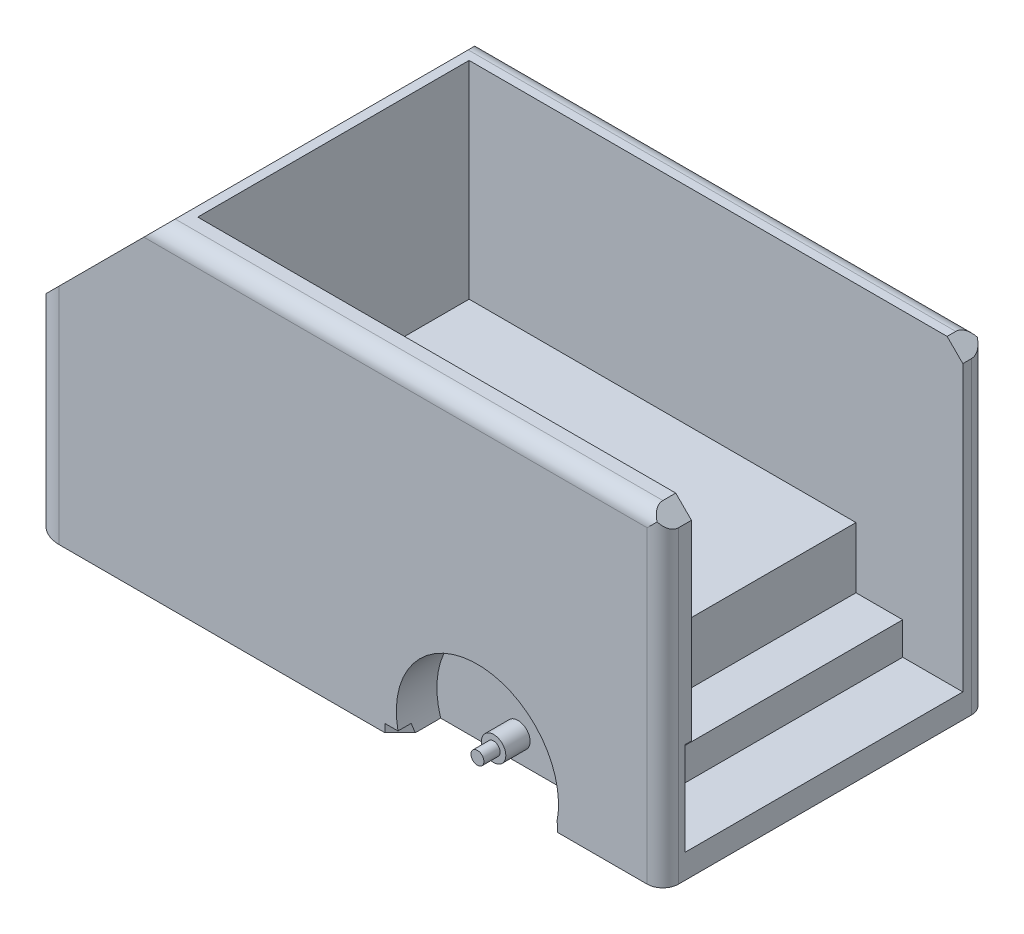
SolidWorks part; units mm, degrees
ref_plane "Front Plane" through (0, 0, 0) normal (0, 0, 1) x (1, 0, 0)
ref_plane "Top Plane" through (0, 0, 0) normal (0, 1, 0) x (1, 0, 0)
ref_plane "Right Plane" through (0, 0, 0) normal (1, 0, 0) x (0, 0, -1)
sketch "Sketch1" plane through (0, 0, 0) normal (0, 1, 0) x (1, 0, 0)
  line L0 (14.509, 50.8) -> (22.488, 42.821)
  line L1 (-101.6, 50.8) -> (14.509, 50.8)
  line L2 (-101.6, 50.8) -> (-101.6, -50.8)
  line L3 (-101.6, -50.8) -> (14.509, -50.8)
  line L4 (101.6, 50.8) -> (101.6, -50.8)
  line L5 (-101.6, 50.8) -> (101.6, -50.8) construction
  line L6 (-101.6, -50.8) -> (101.6, 50.8) construction
  line L7 (22.488, 42.821) -> (37.3964, 42.821)
  line L8 (37.3964, 42.821) -> (37.3964, 38.7247)
  line L9 (37.3964, 38.7247) -> (49.6575, 38.7247)
  line L10 (49.6575, 38.7247) -> (49.6575, 42.821)
  line L11 (49.6575, 42.821) -> (57.4229, 42.821)
  line L13 (-112.3935, 0) -> (135.4852, 0) construction
  line L15 (49.6575, -42.821) -> (57.4229, -42.821)
  line L16 (49.6575, -38.7247) -> (49.6575, -42.821)
  line L17 (37.3964, -38.7247) -> (49.6575, -38.7247)
  line L18 (37.3964, -42.821) -> (37.3964, -38.7247)
  line L19 (22.488, -42.821) -> (37.3964, -42.821)
  line L20 (14.509, -50.8) -> (22.488, -42.821)
  line L21 (68.6622, 50.8) -> (101.6, 50.8)
  line L22 (68.6622, -50.8) -> (101.6, -50.8)
  spline S0 degree 2 poles (57.4229, 42.821) (65.476, 42.6296) (68.6622, 50.8) knots 0 0 0 1 1 1
  spline S1 degree 2 poles (57.4229, -42.821) (65.476, -42.6296) (68.6622, -50.8) knots 0 0 0 1 1 1
  point P0 (0, 0)
  dimension "D1" = 101.6
  dimension "D2" = 203.2
extrude "Boss-Extrude1" add sketch "Sketch1" along normal blind 2.54
sketch "Sketch2" plane through (0, 2.54, 0) normal (0, 1, 0) x (1, 0, 0)
  line L1 (-101.6, 50.8) -> (101.6, 50.8)
  line L2 (-101.6, 50.8) -> (-101.6, -50.8)
  line L3 (-101.6, -50.8) -> (101.6, -50.8)
  line L4 (101.6, 50.8) -> (101.6, -50.8)
extrude "Boss-Extrude2" add sketch "Sketch2" along normal blind 99.06
chamfer "Chamfer2" distance 45.56 angle 45 1 edges at (-101.6, 101.6, 0)
chamfer "Chamfer3" distance 4.92 angle 45 1 edges at (101.6, 101.6, 0)
chamfer "Chamfer4" distance 4.92 angle 45 1 edges at (-101.6, 0, 0)
fillet "Fillet1" radius 4.92 2 edges at (20.32, 101.6, -50.8) (20.32, 101.6, 50.8)
fillet "Fillet3" radius 4.92 2 edges at (101.6, 48.34, 50.8) (101.6, 48.34, -50.8)
chamfer "Chamfer5" distance 10 angle 45 2 edges at (-101.6, 30.48, -50.8) (-101.6, 30.48, 50.8)
fillet "Fillet4" radius 10 6 edges at (-91.6, 33.02, -50.8) (-91.6, 33.02, 50.8) (-101.6, 4.92, 0) (-101.6, 30.48, 40.8) (-101.6, 30.48, -40.8) (-101.6, 56.04, 0)
sketch "Sketch4" plane through (0, 0, 50.8) normal (0, 0, 1) x (1, 0, 0)
  circle A0 centre (43.5269, 7.6872) radius 25.4
  dimension "D1" = 50.8
extrude "Cut-Extrude1" cut sketch "Sketch4" against normal blind 12.7
mirror "Mirror1" about plane through (0, 0, 0) normal (0, 0, 1) of "Cut-Extrude1"
sketch "Sketch5" plane through (0, 0, 38.1) normal (0, 0, 1) x (1, 0, 0)
  circle A0 centre (43.5269, 7.6872) radius 3.81
extrude "Boss-Extrude3" add sketch "Sketch5" along normal blind 7.62
mirror "Mirror2" about plane through (0, 0, 0) normal (0, 0, 1) of "Boss-Extrude3"
sketch "Sketch7" plane through (0, 0, 45.72) normal (0, 0, 1) x (1, 0, 0)
  circle A0 centre (43.5269, 7.6872) radius 2.032
extrude "Boss-Extrude4" add sketch "Sketch7" along normal blind 5.08
mirror "Mirror3" about plane through (0, 0, 0) normal (0, 0, 1) of "Boss-Extrude4"
sketch "Sketch8" plane through (0, 0, 0) normal (0, -1, 0) x (1, 0, 0)
  circle A0 centre (-57.4782, 0) radius 19.05
extrude "Cut-Extrude2" cut sketch "Sketch8" against normal blind 3.81
sketch "Sketch9" plane through (0, 101.6, 0) normal (0, 1, 0) x (1, 0, 0)
  line L1 (-53.0397, 43.1641) -> (132.0445, 43.1641)
  line L2 (-53.0397, 43.1641) -> (-53.0397, -41.8326)
  line L3 (-53.0397, -41.8326) -> (132.0445, -41.8326)
  line L4 (132.0445, 43.1641) -> (132.0445, -41.8326)
extrude "Cut-Extrude3" cut sketch "Sketch9" against normal blind 64.77
sketch "Sketch10" plane through (0, 36.83, 0) normal (0, 1, 0) x (1, 0, 0)
  line L0 (101.6, 43.1641) -> (-53.0397, 43.1641) construction
  line L1 (82.7774, 43.1641) -> (120.2825, 43.1641)
  line L2 (82.7774, 43.1641) -> (82.7774, -43.8299)
  line L3 (82.7774, -43.8299) -> (120.2825, -43.8299)
  line L4 (120.2825, 43.1641) -> (120.2825, -43.8299)
extrude "Cut-Extrude4" cut sketch "Sketch10" against normal blind 29.21
sketch "Sketch11" plane through (0, 36.83, 0) normal (0, 1, 0) x (1, 0, 0)
  line L0 (96.68, 43.1641) -> (-53.0397, 43.1641) construction
  line L1 (68.1305, 43.1641) -> (93.8736, 43.1641)
  line L2 (68.1305, 43.1641) -> (68.1305, -41.8326)
  line L3 (68.1305, -41.8326) -> (93.8736, -41.8326)
  line L4 (93.8736, 43.1641) -> (93.8736, -41.8326)
  line L5 (-53.0397, -41.8326) -> (96.68, -41.8326) construction
extrude "Cut-Extrude5" cut sketch "Sketch11" against normal blind 19.05
